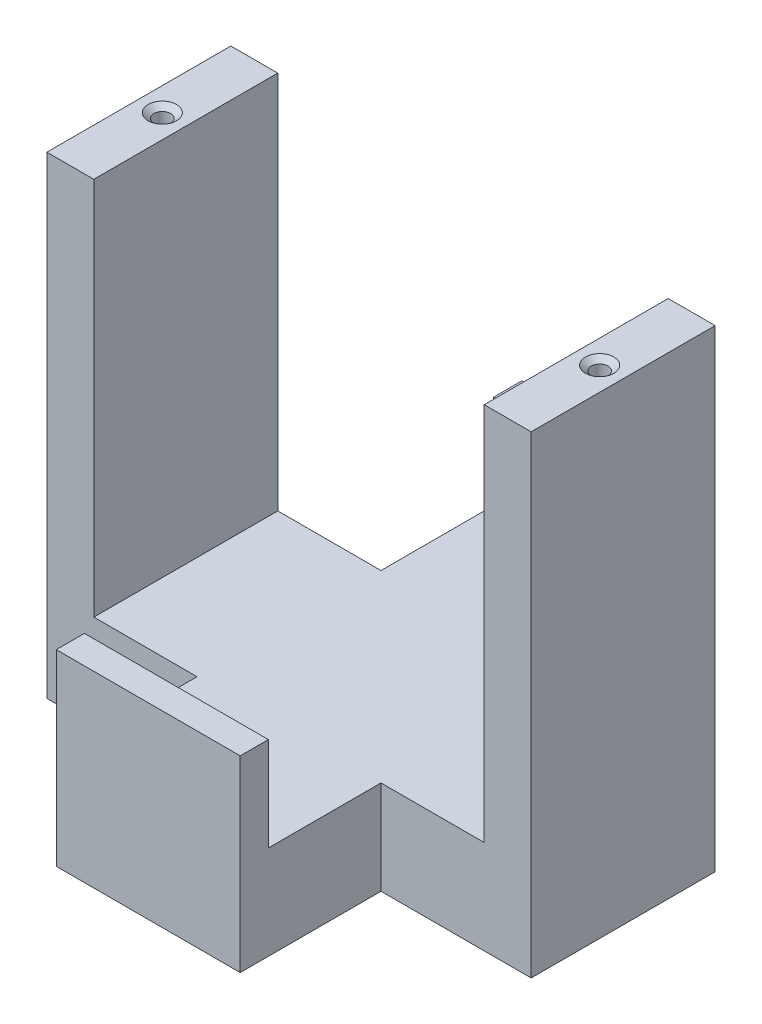
SolidWorks part; units mm, degrees
ref_plane "Plano frontal" through (0, 0, 0) normal (0, 0, 1) x (1, 0, 0)
ref_plane "Plano superior" through (0, 0, 0) normal (0, 1, 0) x (1, 0, 0)
ref_plane "Plano direito" through (0, 0, 0) normal (1, 0, 0) x (0, 0, -1)
sketch "Esboço1" plane through (0, 0, 0) normal (0, 1, 0) x (1, 0, 0)
  line L12 (0, 0) -> (20.8, 0) construction
  line L13 (0, 0) -> (-20.8, 0) construction
  line L14 (0, 0) -> (0, 21.8) construction
  line L15 (0, 0) -> (0, -21.8) construction
  line L18 (-9.8, 21.8) -> (-9.8, 9.8)
  line L19 (-9.8, 9.8) -> (-20.8, 9.8)
  line L28 (-20.8, 9.8) -> (-20.8, -9.8)
  line L29 (-9.8, 21.8) -> (9.8, 21.8)
  line L30 (20.8, 9.8) -> (20.8, -9.8)
  line L31 (9.8, 9.8) -> (20.8, 9.8)
  line L32 (9.8, 21.8) -> (9.8, 9.8)
  line L33 (9.8, -21.8) -> (9.8, -9.8)
  line L34 (9.8, -9.8) -> (20.8, -9.8)
  line L35 (-9.8, -21.8) -> (9.8, -21.8)
  line L36 (-9.8, -9.8) -> (-20.8, -9.8)
  line L37 (-9.8, -21.8) -> (-9.8, -9.8)
  dimension "D1" = 9.8
  dimension "D2" = 9.8
  dimension "D3" = 11
  dimension "D4" = 12
extrude "Ressalto-extrusão1" add sketch "Esboço1" along normal blind 10
sketch "Esboço2" plane through (0, 0, 0) normal (0, 1, 0) x (1, 0, 0)
  line L0 (0, 21.8) -> (0, -21.8) construction
  line L1 (-9.8, -21.8) -> (9.8, -21.8) construction
  line L2 (9.8, 21.8) -> (-9.8, 21.8) construction
  line L3 (25.8, 9.8) -> (25.8, -9.8)
  line L4 (-20.8, 9.8) -> (-25.8, 9.8)
  line L5 (-20.8, 9.8) -> (-20.8, -9.8)
  line L6 (-20.8, -9.8) -> (-25.8, -9.8)
  line L7 (-25.8, 9.8) -> (-25.8, -9.8)
  line L8 (20.8, -9.8) -> (25.8, -9.8)
  line L9 (20.8, 9.8) -> (20.8, -9.8)
  line L10 (20.8, 9.8) -> (25.8, 9.8)
  dimension "D1" = 19.6
  dimension "D2" = 5
extrude "Ressalto-extrusão2" add sketch "Esboço2" along normal blind 50.4
sketch "Esboço3" plane through (0, 10, 0) normal (0, 1, 0) x (1, 0, 0)
  line L0 (-9.8, 21.8) -> (-9.8, 24.8)
  line L1 (-9.8, 24.8) -> (9.8, 24.8)
  line L2 (9.8, 24.8) -> (9.8, 21.8)
  line L3 (9.8, 21.8) -> (-9.8, 21.8)
  line L4 (25.8, 0) -> (-25.8, 0) construction
  line L5 (25.8, -9.8) -> (25.8, 9.8) construction
  line L6 (-25.8, 9.8) -> (-25.8, -9.8) construction
  line L7 (9.8, -21.8) -> (-9.8, -21.8)
  line L8 (9.8, -24.8) -> (9.8, -21.8)
  line L9 (-9.8, -24.8) -> (9.8, -24.8)
  line L10 (-9.8, -21.8) -> (-9.8, -24.8)
  dimension "D1" = 3
  dimension "D2" = 19.6
extrude "Ressalto-extrusão3" add sketch "Esboço3" along normal blind 10 and the other way blind 10
sketch "Esboço4" plane through (0, 50.4, 0) normal (0, 1, 0) x (1, 0, 0)
  line L0 (-23.3, 9.8) -> (-23.3, -9.8) construction
  line L1 (-20.8, 9.8) -> (-25.8, 9.8) construction
  line L2 (-25.8, -9.8) -> (-20.8, -9.8) construction
  line L3 (-20.8, 0) -> (-25.8, 0) construction
  line L4 (-20.8, 9.8) -> (-20.8, -9.8) construction
  line L5 (-25.8, 9.8) -> (-25.8, -9.8) construction
  line L6 (0, -24.8) -> (0, 24.8) construction
  line L7 (-9.8, -24.8) -> (9.8, -24.8) construction
  line L8 (9.8, 24.8) -> (-9.8, 24.8) construction
  circle A0 centre (-23.3, 0) radius 1.5
  circle A1 centre (23.3, 0) radius 1.5
  point P0 (-23.3, 0)
  point P8 (23.3, 0)
  dimension "D1" = 3
hole_wizard "Escareado para parafuso de máquina com cabeça chata (100) de #01" positions "Esboço4" profile "Esboço6" countersink size "#0" standard "Superior"
sketch "Esboço6" plane through (-23.3, 50.4, 0) normal (1, 0, 0) x (0, 0, 1)
  line L0 (0, 0) -> (0, 5.5342)
  line L1 (0, 5.5342) -> (0.889, 5)
  line L2 (0.889, 5) -> (0.889, 0.5222)
  line L3 (0.889, 0.5222) -> (1.5113, 0)
  line L5 (1.5113, 0) -> (0, 0)
  line L6 (-0.889, 0.5222) -> (-1.5113, 0) construction
  line L10 (0, 5.5342) -> (-0.889, 5) construction
  line L11 (0, -6.35) -> (0, 107.95) construction
  dimension "Hole Dia." = 1.778
  dimension "Hole Depth" = 5
  dimension "Near C'Sink Dia." = 3.0226
  dimension "Near C'Sink Angle" = 100
  dimension "Drill Angle" = 118
sketch "Esboço9" plane through (0, 0, 0) normal (0, -1, 0) x (-1, 0, 0)
  line L0 (-17.8, 9.8) -> (-17.8, -9.8) construction
  line L1 (-25.8, 9.8) -> (-9.8, 9.8) construction
  line L2 (-9.8, -9.8) -> (-25.8, -9.8) construction
  line L4 (0, 0) -> (-25.8, 0) construction
  line L5 (-25.8, -9.8) -> (-25.8, 9.8) construction
  line L7 (0, 0) -> (25.8, 0) construction
  line L8 (25.8, 9.8) -> (25.8, -9.8) construction
  line L10 (17.8, 9.8) -> (17.8, -9.8) construction
  line L11 (9.8, 9.8) -> (25.8, 9.8) construction
  line L12 (25.8, -9.8) -> (9.8, -9.8) construction
  point P0 (-17.8, 0)
  point P39 (17.8, 0)
hole_wizard "Escareado para parafuso de máquina com cabeça chata (100) de #02" positions "Esboço9" profile "Esboço8" countersink size "#0" standard "Superior"
sketch "Esboço8" plane through (17.8, 0, 0) normal (1, 0, 0) x (0, 0, -1)
  line L0 (0, 0) -> (0, 5.5342)
  line L1 (0, 5.5342) -> (0.889, 5)
  line L2 (0.889, 5) -> (0.889, 0.5222)
  line L3 (0.889, 0.5222) -> (1.5113, 0)
  line L5 (1.5113, 0) -> (0, 0)
  line L6 (-0.889, 0.5222) -> (-1.5113, 0) construction
  line L10 (0, 5.5342) -> (-0.889, 5) construction
  line L11 (0, -6.35) -> (0, 107.95) construction
  dimension "Hole Dia." = 1.778
  dimension "Hole Depth" = 5
  dimension "Near C'Sink Dia." = 3.0226
  dimension "Near C'Sink Angle" = 100
  dimension "Drill Angle" = 118
